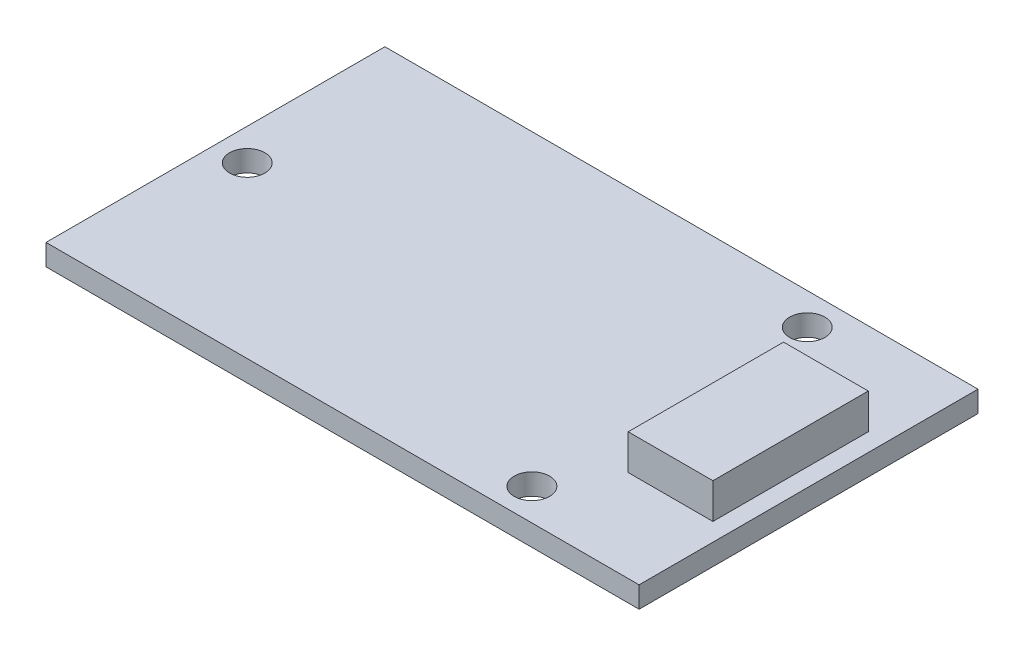
SolidWorks part; units mm, degrees
ref_plane "Front Plane" through (0, 0, 0) normal (0, 0, 1) x (1, 0, 0)
ref_plane "Top Plane" through (0, 0, 0) normal (0, 1, 0) x (1, 0, 0)
ref_plane "Right Plane" through (0, 0, 0) normal (1, 0, 0) x (0, 0, -1)
sketch "Sketch2" plane through (0, 0, 0) normal (0, 1, 0) x (1, 0, 0)
  line L1 (0, 0) -> (42, 0)
  line L2 (0, 0) -> (0, -24)
  line L3 (0, -24) -> (42, -24)
  line L4 (42, 0) -> (42, -24)
  line L6 (40.7285, -6.5) -> (34.7285, -6.5)
  line L7 (40.7285, -6.5) -> (40.7285, -17.5)
  line L8 (40.7285, -17.5) -> (34.7285, -17.5)
  line L9 (34.7285, -6.5) -> (34.7285, -17.5)
  circle A6 centre (32.16, -2.25) radius 1.25
  circle A8 centre (32.16, -21.75) radius 1.25
  circle A9 centre (2.25, -12) radius 1.25
  dimension "D3" = 2.5
  dimension "D6" = 9.84
  dimension "D5" = 11
  dimension "D7" = 2.25
  dimension "D9" = 6
  dimension "D1" = 42
  dimension "D2" = 24
  dimension "D8" = 2.25
  dimension "D10" = 6.5
  dimension "D11" = 34.7285
extrude "Boss-Extrude1" add sketch "Sketch2" along normal blind 1.5 contours A6 | L7 L6 L9 L8 region at (19.7904, 0, 12)
extrude "Boss-Extrude2" add sketch "Sketch2<9>" along normal blind 4 contours L9 L8 L7 L6
sketch "Sketch2<9>" plane through (0, 0, 0) normal (0, 1, 0) x (1, 0, 0) same geometry as "Sketch2"
